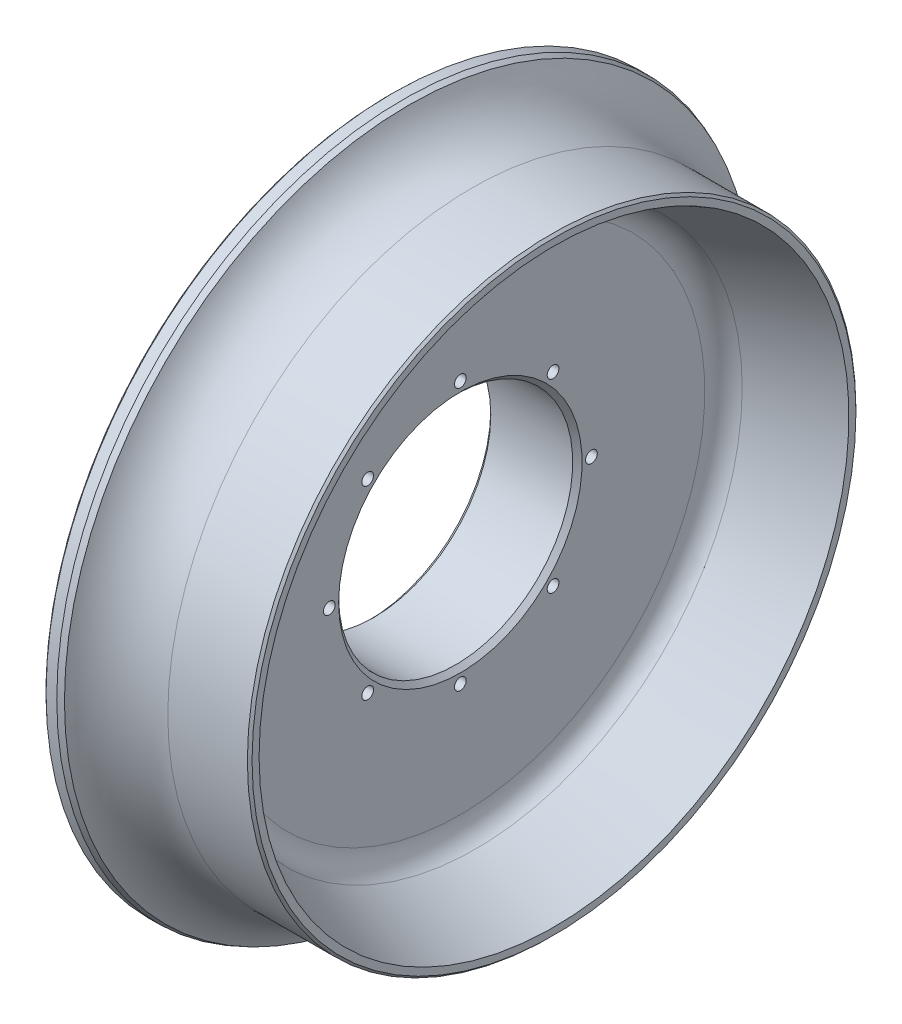
SolidWorks part; units mm, degrees
material "POM Acetal kopolimer"
ref_plane "Front" through (0, 0, 0) normal (0, 0, 1) x (1, 0, 0)
ref_plane "Top" through (0, 0, 0) normal (0, 1, 0) x (1, 0, 0)
ref_plane "Right" through (0, 0, 0) normal (1, 0, 0) x (0, 0, -1)
sketch "Szkic1" plane through (0, 0, 0) normal (0, 0, 1) x (1, 0, 0)
  line L0 (39, 50) -> (39, 104.4391)
  line L1 (0, 0) -> (85, 0) construction
  line L2 (79, 130) -> (79, 126)
  line L3 (0, 50) -> (39, 50)
  line L6 (44, 130) -> (79, 130)
  line L7 (79, 126) -> (45.5798, 113.836)
  line L8 (9, 148) -> (9, 140)
  line L11 (0, 63) -> (0, 50)
  line L12 (0, 63) -> (19, 63)
  line L13 (9, 140) -> (26.0711, 122.9289)
  line L14 (29, 115.8579) -> (29, 73)
  line L15 (9, 148) -> (16.5045, 148)
  arc A0 (16.5045, 148) -> (44, 130) centre (44, 160) ccw
  arc A1 (19, 63) -> (29, 73) centre (19, 73) ccw
  arc A2 (29, 115.8579) -> (26.0711, 122.9289) centre (19, 115.8579) ccw
  arc A3 (45.5798, 113.836) -> (39, 104.4391) centre (49, 104.4391) ccw
  dimension "D1" = 50
  dimension "D2" = 13
  dimension "D3" = 39
revolve "Obrót1" add sketch "Szkic1" angle 360 about L1
sketch "Szkic2" plane through (0, 0, 0) normal (-1, 0, 0) x (0, 0, 1)
  circle A0 centre (0, 56) radius 2.5
  circle A1 centre (39.598, 39.598) radius 2.5
  circle A2 centre (56, 0) radius 2.5
  circle A3 centre (39.598, -39.598) radius 2.5
  circle A4 centre (0, -56) radius 2.5
  circle A5 centre (-39.598, -39.598) radius 2.5
  circle A6 centre (-56, 0) radius 2.5
  circle A7 centre (-39.598, 39.598) radius 2.5
  point P19 (0, 0)
  dimension "D1" = 56
  dimension "D2" = 5
  dimension "D3" = 8
extrude "Wytnij-wyciągnięcie1" cut sketch "Szkic2" against normal through all
chamfer "Sfazowanie1" distance 1 angle 45 4 edges at (79, 0, 130) (16.5045, 0, 148) (9, 0, 148) (0, 0, 63) first distance on face at (79, 0, 130) first distance on face at (16.5045, 0, 148) first distance on face at (9, 0, 148) first distance on face at (0, 0, 63)
chamfer "Sfazowanie2" distance 2 angle 45 2 edges at (39, 0, 50) (0, 0, 50)
